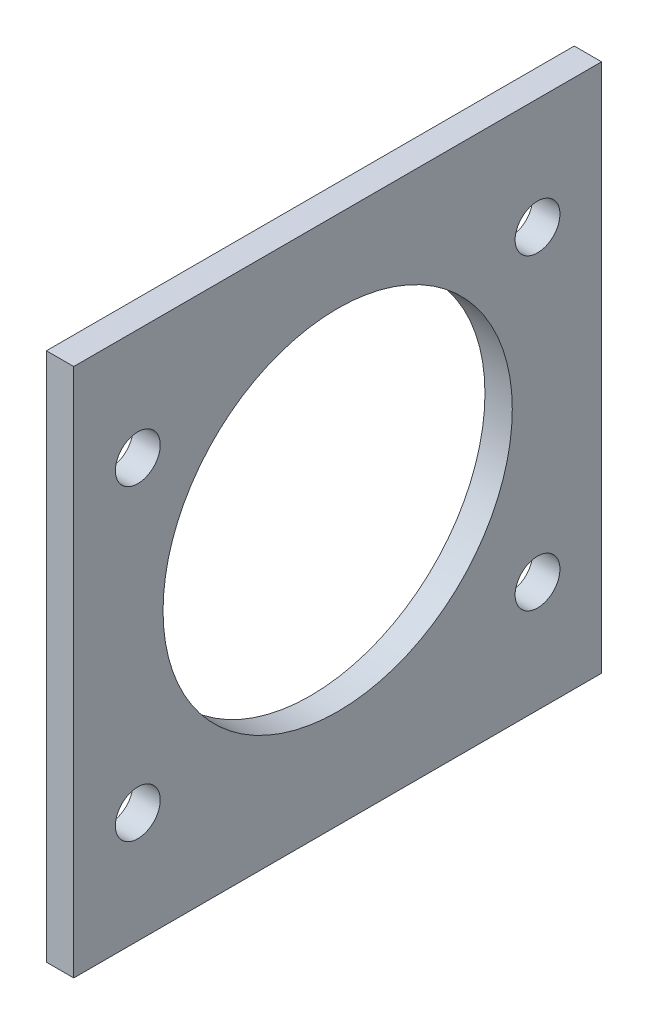
SolidWorks part; units mm, degrees
material "AISI 304"
ref_plane "Front Plane" through (0, 0, 0) normal (0, 0, 1) x (1, 0, 0)
ref_plane "Top Plane" through (0, 0, 0) normal (0, 1, 0) x (1, 0, 0)
ref_plane "Right Plane" through (0, 0, 0) normal (1, 0, 0) x (0, 0, -1)
sketch "Sketch1" plane through (0, 0, 0) normal (1, 0, 0) x (0, 0, -1)
  line L1 (0, 0) -> (61.8, 0)
  line L2 (0, 0) -> (0, 62)
  line L3 (0, 62) -> (61.8, 62)
  line L4 (61.8, 0) -> (61.8, 62)
  dimension "D1" = 61.8
  dimension "D2" = 62
extrude "Boss-Extrude1" add sketch "Sketch1" along normal blind 3.2
sketch "Sketch2" plane through (3.2, 0, 0) normal (1, 0, 0) x (0, 0, -1)
  line L0 (30.9, 62) -> (30.9, 0) construction
  line L1 (61.8, 62) -> (0, 62) construction
  line L2 (0, 0) -> (61.8, 0) construction
  circle A0 centre (30.9, 32) radius 20.445
  point P13 (30.9, 0)
  dimension "D1" = 20.445
  dimension "D2" = 30
extrude "Cut-Extrude1" cut sketch "Sketch2" against normal up to next
sketch "Sketch3" plane through (0, 0, 0) normal (-1, 0, 0) x (0, 0, 1)
  circle A0 centre (-54.3, 49) radius 2.625
  circle A1 centre (-54.3, 13) radius 2.625
  circle A2 centre (-7.5, 49) radius 2.625
  circle A3 centre (-7.5, 13) radius 2.625
extrude "Cut-Extrude2" cut sketch "Sketch3" against normal up to next
